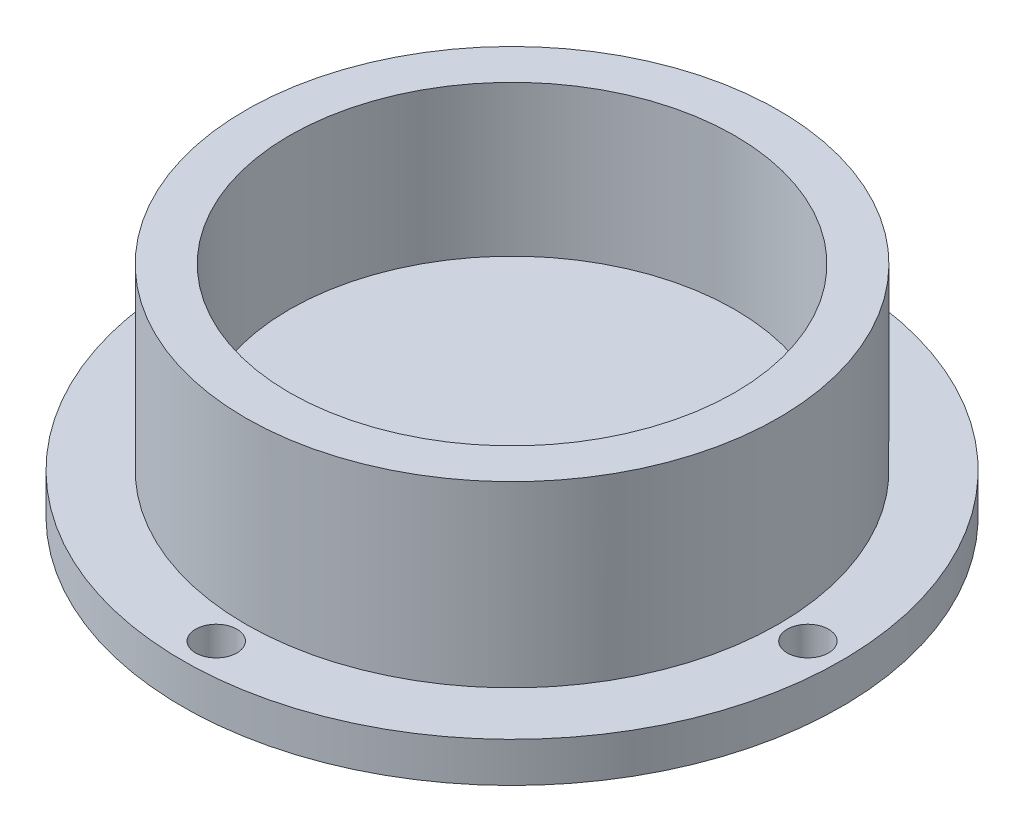
SolidWorks part; units mm, degrees
ref_plane "Plan de face" through (0, 0, 0) normal (0, 0, 1) x (1, 0, 0)
ref_plane "Plan de dessus" through (0, 0, 0) normal (0, 1, 0) x (1, 0, 0)
ref_plane "Plan de droite" through (0, 0, 0) normal (1, 0, 0) x (0, 0, -1)
sketch "Esquisse1" plane through (0, 0, 0) normal (0, 1, 0) x (1, 0, 0)
  circle A0 centre (0, 0) radius 10
  dimension "D1" = 20
extrude "Boss.-Extru.1" add sketch "Esquisse1" against normal blind 8.2
sketch "Esquisse2" plane through (0, 0, 0) normal (0, 1, 0) x (1, 0, 0)
  circle A0 centre (0, 0) radius 8.354
  dimension "D1" = 16.708
extrude "Enlèv. mat.-Extru.1" cut sketch "Esquisse2" against normal blind 5.65
sketch "Esquisse3" plane through (0, -8.2, 0) normal (0, -1, 0) x (-1, 0, 0)
  circle A0 centre (0, 0) radius 12.3661
extrude "Boss.-Extru.3" add sketch "Esquisse3" against normal blind 1.5
sketch "Esquisse4" plane through (0, -6.7, 0) normal (0, 1, 0) x (1, 0, 0)
  circle A0 centre (0, 11.1) radius 0.775
  circle A1 centre (11.1, 0) radius 0.775
  circle A2 centre (0, -11.1) radius 0.775
  circle A3 centre (-11.1, 0) radius 0.775
  point P12 (0, 0)
  dimension "D2" = 1.55
  dimension "D1" = 11.1
  dimension "D3" = 4
extrude "Enlèv. mat.-Extru.2" cut sketch "Esquisse4" against normal up to surface (1.5 mm away) up to face at (0, -8.2, -12.3661)
equation "\"D1@Esquisse1\"=20mm"
equation "\"D1@Esquisse2\"=16.2mm + 20mil"
